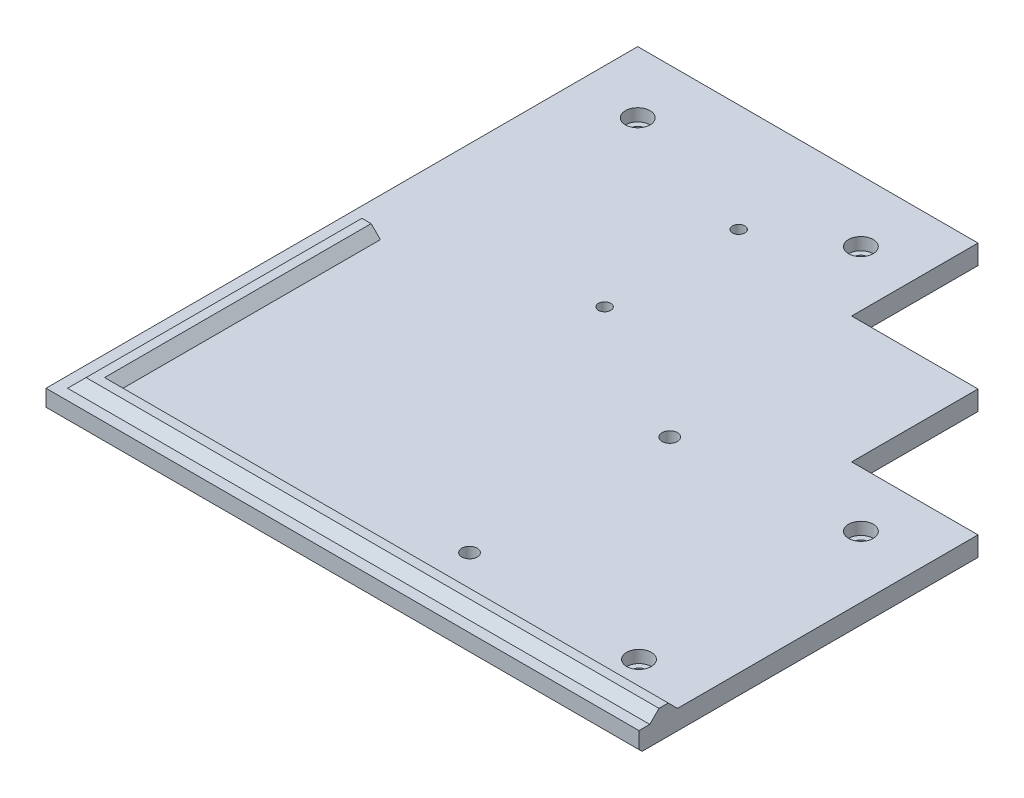
SolidWorks part; units mm, degrees
ref_plane "Front Plane" through (0, 0, 0) normal (0, 0, 1) x (1, 0, 0)
ref_plane "Top Plane" through (0, 0, 0) normal (0, 1, 0) x (1, 0, 0)
ref_plane "Right Plane" through (0, 0, 0) normal (1, 0, 0) x (0, 0, -1)
sketch "Sketch1" plane through (0, 0, 0) normal (0, 1, 0) x (1, 0, 0)
  line L1 (-96.2, 96) -> (96.2, 96)
  line L2 (-96.2, 96) -> (-96.2, -96)
  line L3 (-96.2, -96) -> (96.2, -96)
  line L4 (96.2, 96) -> (96.2, -96)
  line L5 (-96.2, 96) -> (96.2, -96) construction
  line L6 (-96.2, -96) -> (96.2, 96) construction
  point P0 (0, 0)
  dimension "D1" = 192
  dimension "D2" = 192.4
extrude "Boss-Extrude1" add sketch "Sketch1" along normal blind 6.35
sketch "Sketch2" plane through (0, 6.35, 0) normal (0, 1, 0) x (1, 0, 0)
  line L1 (-96.2, 96) -> (-55.2, 96)
  line L2 (-96.2, 96) -> (-96.2, 55)
  line L3 (-96.2, 55) -> (-55.2, 55) construction
  line L4 (-55.2, 96) -> (-55.2, 55) construction
  line L5 (-96.2, 55) -> (-55.2, 55)
  line L6 (-96.2, 55) -> (-96.2, 14)
  line L7 (-96.2, 14) -> (-55.2, 14)
  line L8 (-55.2, 55) -> (-55.2, 14)
  line L9 (-55.2, 96) -> (-14.2, 96)
  line L10 (-55.2, 96) -> (-55.2, 55)
  line L11 (-55.2, 55) -> (-14.2, 55)
  line L12 (-14.2, 96) -> (-14.2, 55)
  line M14 (96.2, 96) -> (-96.2, 96)
  line M15 (-96.2, 96) -> (-96.2, -96)
  dimension "D1" = 41
extrude "Cut-Extrude1" cut sketch "Sketch2" against normal up to next contours L8 L5 L7 M15 | L10 L5 M14 M15 | L12 L10 L11 M14 region at (-75.7, 6.35, -75.5) region at (-34.7, 6.35, -75.5) region at (-75.7, 6.35, -34.5)
sketch "Sketch3" plane through (0, 6.35, 0) normal (0, 1, 0) x (1, 0, 0)
  line L0 (-96.2, 76) -> (96.2, 76) construction
  line L1 (-96.2, 96) -> (-56.2, 96) construction
  line L2 (-96.2, 96) -> (-96.2, -96) construction
  line L3 (-96.2, -96) -> (-56.2, -96) construction
  line L4 (96.2, 96) -> (-96.2, 96)
  line L5 (96.2, -96) -> (96.2, 96)
  line L6 (-96.2, -96) -> (96.2, -96)
  line L7 (-96.2, 96) -> (-96.2, -96)
  line L8 (96.2, 96) -> (-96.2, 96) construction
  line L9 (96.2, -96) -> (96.2, 96) construction
  line L10 (-96.2, -96) -> (96.2, -96) construction
  line L11 (-96.2, 96) -> (-96.2, -96) construction
  line L12 (-56.2, 96) -> (-56.2, -96) construction
  line L13 (-96.2, 96) -> (96.2, 96) construction
  line L14 (-96.2, 96) -> (-96.2, 56) construction
  line L15 (-96.2, 56) -> (96.2, 56) construction
  line L16 (96.2, 96) -> (96.2, 56) construction
  line L17 (-76.2, 96) -> (-76.2, -96) construction
  point P20 (-76.2, -4)
  point P22 (-76.2, -76)
  point P24 (3.8, 76)
  point P26 (76.2, 76)
  dimension "D2" = 40
  dimension "D3" = 40
  dimension "D4" = 20
  dimension "D5" = 60
  dimension "D6" = 60
  dimension "D7" = 20
  dimension "D8" = 20
  dimension "D1" = 0
hole_wizard "CBORE for M4 SHCS1" positions "Sketch3" profile "Sketch4" counterbore size "M4" standard "ANSI Metric" end condition up to next
sketch "Sketch4" plane through (76.2, 6.35, -76) normal (1, 0, 0) x (0, 0, 1)
  line L0 (0, 0) -> (0, 6.35)
  line L1 (0, 6.35) -> (2.25, 6.35)
  line L3 (2.25, 6.35) -> (2.25, 4)
  line L4 (2.25, 4) -> (4, 4)
  line L5 (4, 4) -> (4, 0)
  line L7 (4, 0) -> (0, 0)
  line L11 (0, -6.35) -> (0, 107.95) construction
  dimension "Thru Hole Dia." = 4.5
  dimension "Thru Hole Depth" = 6.35
  dimension "C'Bore Dia." = 8
  dimension "C'Bore Depth" = 4
mirror "Mirror1" [suppressed] of bodies 105
delete or keep bodies "Body-Delete/Keep 1" [suppressed] type delete bodies bodies 105
mirror "Mirror2" [suppressed] of bodies 108
delete or keep bodies "Body-Delete/Keep 2" [suppressed] type delete bodies bodies 108
sketch "Sketch5" plane through (0, 6.35, 0) normal (0, 1, 0) x (1, 0, 0)
  line L0 (-18.7, -8.525) -> (-18.7, -73.475) construction
  line L1 (-56.2, -4.375) -> (18.8, -4.375) construction
  line L2 (-56.2, -4.375) -> (-56.2, -77.625) construction
  line L3 (-56.2, -77.625) -> (18.8, -77.625) construction
  line L4 (18.8, -4.375) -> (18.8, -77.625) construction
  line L5 (-96.2, -41) -> (96.2, -41) construction
  line L6 (-96.2, 14) -> (-96.2, -96) construction
  line L7 (96.2, -96) -> (96.2, 96) construction
  line L8 (-56.2, -41) -> (18.8, -41) construction
  circle A0 centre (-18.7, -8.525) radius 2.5
  circle A1 centre (-18.7, -73.475) radius 2.5
  point P12 (-18.7, -41)
  point P15 (-18.7, -41)
  dimension "D4" = 5
  dimension "D1" = 73.25
  dimension "D2" = 75
  dimension "D3" = 40
  dimension "D5" = 64.95
extrude "Cut-Extrude2" cut sketch "Sketch5" against normal blind 6
sketch "Sketch6" plane through (0, 0.35, 0) normal (0, 1, 0) x (1, 0, 0)
  circle A0 centre (-18.7, -8.525) radius 2.25
  circle A1 centre (-18.7, -73.475) radius 2.25
  dimension "D1" = 4.5
extrude "Cut-Extrude3" cut sketch "Sketch6" against normal up to next
sketch "Sketch7" plane through (0, 6.35, 0) normal (0, 1, 0) x (1, 0, 0)
  line L0 (96.2, -96) -> (96.2, 96) construction
  line L1 (28.45, 61) -> (163.95, 61) construction
  line L2 (28.45, 61) -> (28.45, 17.5) construction
  line L3 (28.45, 17.5) -> (163.95, 17.5) construction
  line L4 (163.95, 61) -> (163.95, 17.5) construction
  line L5 (28.45, 61) -> (163.95, 17.5) construction
  line L6 (28.45, 17.5) -> (163.95, 61) construction
  line L7 (96.2, 96) -> (-14.2, 96) construction
  circle A0 centre (28.45, 61) radius 1.75
  circle A1 centre (28.45, 17.5) radius 1.75
  point P0 (96.2, 39.25)
  dimension "D4" = 3.5
  dimension "D1" = 43.5
  dimension "D2" = 135.5
  dimension "D3" = 35
extrude "Cut-Extrude4" cut sketch "Sketch7" against normal up to next
sketch "Sketch8" plane through (0, 6.35, 0) normal (0, 1, 0) x (1, 0, 0)
  circle A0 centre (28.45, 61) radius 2
  circle A1 centre (28.45, 17.5) radius 2
  dimension "D1" = 4
extrude "Cut-Extrude5" cut sketch "Sketch8" against normal blind 5
sketch "Sketch9" plane through (0, 6.35, 0) normal (0, 1, 0) x (1, 0, 0)
  line L2 (0, 0) -> (96.2, 0) construction
  line L3 (96.2, -96) -> (96.2, 96) construction
  line L4 (-96.2, -88) -> (88.2, -88)
  line L5 (88.2, -88) -> (88.2, 96)
  line L6 (-96.2, -88) -> (88.2, -88)
  line L7 (88.2, -88) -> (88.2, 0)
  dimension "D1" = 8
extrude "Extrude-Thin1" add sketch "Sketch9" along normal blind 3 thin thin type mid plane wall 3
chamfer "Chamfer1" distance 3 angle 45 4 edges at (-4.75, 6.35, 86.5) (86.7, 6.35, 43.25) (-3.25, 6.35, 89.5) (89.7, 6.35, 44.75)
chamfer "Chamfer2" distance 1 angle 45 2 edges at (0, 0, 96) (96.2, 0, 0)
mirror "Mirror3" about plane through (96.2, 6.35, -96) normal (-1, 0, 0) of bodies 115 113
delete or keep bodies "Body-Delete/Keep 4" type delete bodies bodies 115
equation "\"D2@Sketch1\"=384.8/2"
